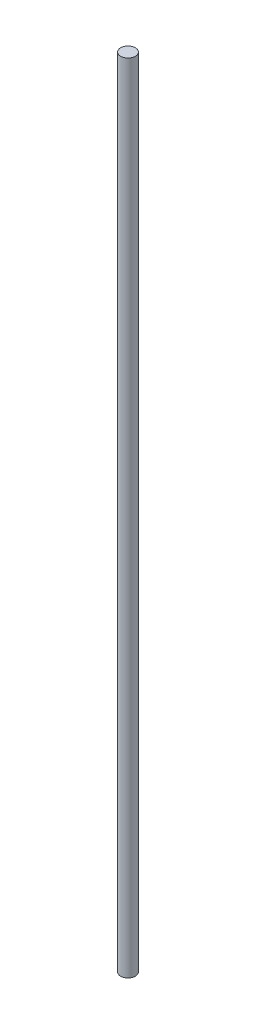
SolidWorks part; units mm, degrees
ref_plane "Front Plane" through (0, 0, 0) normal (0, 0, 1) x (1, 0, 0)
ref_plane "Top Plane" through (0, 0, 0) normal (0, 1, 0) x (1, 0, 0)
ref_plane "Right Plane" through (0, 0, 0) normal (1, 0, 0) x (0, 0, -1)
sketch "Sketch1" plane through (0, 0, 0) normal (0, 1, 0) x (1, 0, 0)
  circle A0 centre (0, 0) radius 1.5875
  dimension "D1" = 3.175
extrude "Boss-Extrude1" add sketch "Sketch1" along normal blind 171.45
